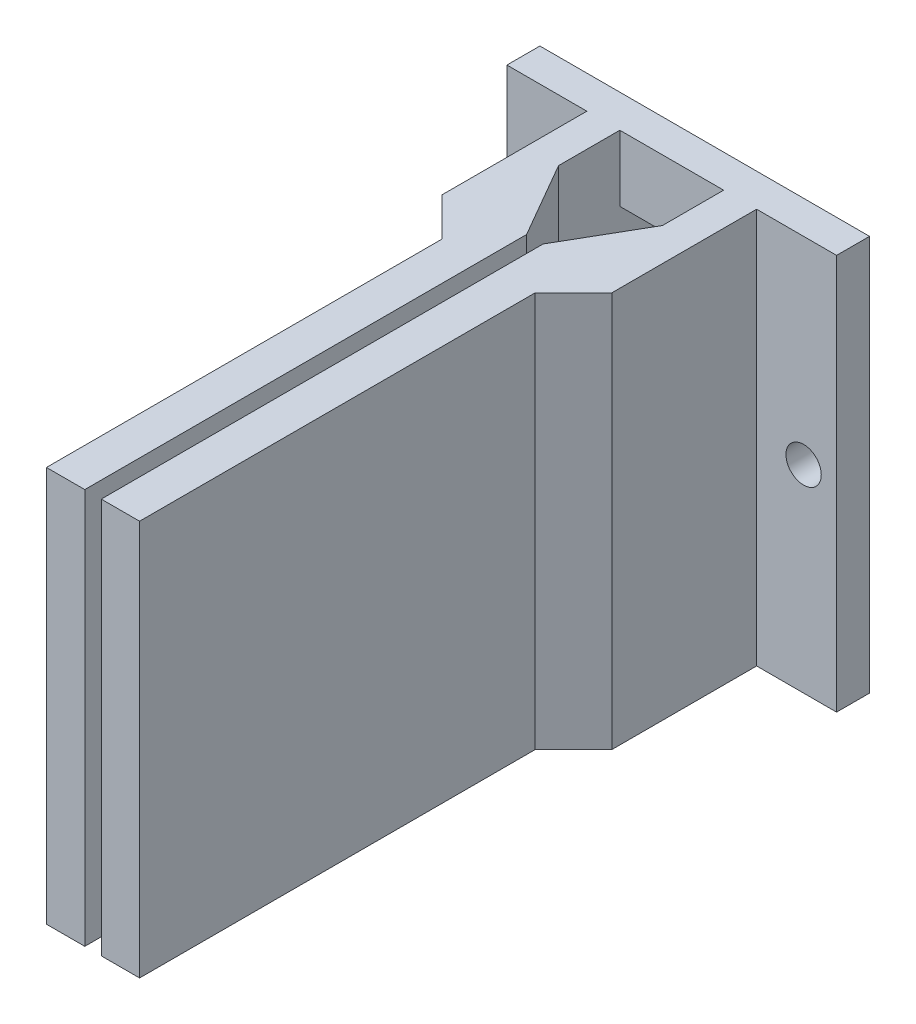
SolidWorks part; units mm, degrees
ref_plane "Front Plane" through (0, 0, 0) normal (0, 0, 1) x (1, 0, 0)
ref_plane "Top Plane" through (0, 0, 0) normal (0, 1, 0) x (1, 0, 0)
ref_plane "Right Plane" through (0, 0, 0) normal (1, 0, 0) x (0, 0, -1)
sketch "Sketch1" plane through (0, 0, 0) normal (0, 0, 1) x (1, 0, 0)
  line L1 (-5, -82.275) -> (5, -82.275)
  line L2 (-5, -82.275) -> (-5, 82.275)
  line L3 (-5, 82.275) -> (5, 82.275)
  line L4 (5, -82.275) -> (5, 82.275)
  line L5 (-5, -82.275) -> (5, 82.275) construction
  line L6 (-5, 82.275) -> (5, -82.275) construction
  line L7 (-5, 82.275) -> (5, 82.275)
  line L8 (-5, 82.275) -> (-5, 88.275)
  line L9 (-5, 88.275) -> (5, 88.275)
  line L10 (5, 82.275) -> (5, 88.275)
  circle A0 centre (0, 82.275) radius 2.5
  point P0 (0, 0)
  dimension "D3" = 5
  dimension "D1" = 164.55
  dimension "D2" = 10
  dimension "D4" = 6
extrude "Boss-Extrude1" add sketch "Sketch1" along normal blind 2 contours A0 L3 L2 L1 L4 | A0 L3 L10 L9 L8 region at (0, -0.4875, 0) region at (0, 85.6543, 0)
sketch "Sketch2" plane through (0, 0, 0) normal (0, 0, -1) x (-1, 0, 0)
  line L4 (5, 88.275) -> (-5, 88.275)
  line L5 (-5, 88.275) -> (-5, -82.275)
  line L6 (-5, -82.275) -> (5, -82.275)
  line L7 (5, -82.275) -> (5, 88.275)
  line L8 (5, 88.275) -> (-5, 88.275)
  line L9 (-5, 88.275) -> (-5, -82.275)
  line L10 (-5, -82.275) -> (5, -82.275)
  line L11 (5, -82.275) -> (5, 88.275)
  circle A0 centre (0, 82.275) radius 2.95
  dimension "D2" = 5.9
  dimension "D1" = 0
extrude "Boss-Extrude2" add sketch "Sketch2" along normal blind 1
sketch "Sketch3" plane through (0, -82.275, 0) normal (0, -1, 0) x (1, 0, 0)
  line L0 (5, -1) -> (-5, -1) construction
  line L1 (34.925, 9.16) -> (-34.925, 9.16)
  line L2 (34.925, 9.16) -> (34.925, -1)
  line L3 (34.925, -1) -> (-34.925, -1)
  line L4 (-34.925, 9.16) -> (-34.925, -1)
  circle A0 centre (28.575, 4.08) radius 1.8605
  circle A1 centre (-28.575, 4.08) radius 1.8605
  point P4 (0, -1)
  point P7 (0, -1)
  dimension "D3" = 3.7211
  dimension "D1" = 69.85
  dimension "D2" = 57.15
  dimension "D4" = 28.575
  dimension "D5" = 5.08
  dimension "D6" = 5.08
extrude "Boss-Extrude3" add sketch "Sketch3" against normal blind 2.5
fillet "Fillet1" radius 12.7 3 edges at (-5, -79.775, 0.5) (5, -79.775, 0.5) (0, -79.775, 2)
sketch "Sketch4" plane through (0, 0, -1) normal (0, 0, -1) x (-1, 0, 0)
  line L0 (5, -67.075) -> (5, 88.275) construction
  line L1 (8.175, 101.325) -> (5, 101.325)
  line L2 (8.175, 101.325) -> (8.175, 63.225)
  line L3 (8.175, 63.225) -> (5, 63.225)
  line L4 (5, 101.325) -> (5, 63.225)
  line L5 (-5, 101.325) -> (-8.175, 101.325)
  line L6 (-5, 101.325) -> (-5, 63.225)
  line L7 (-5, 63.225) -> (-8.175, 63.225)
  line L8 (-8.175, 101.325) -> (-8.175, 63.225)
  line L9 (-5, -67.075) -> (-5, 88.275) construction
  line L11 (5, 101.325) -> (-5, 101.325)
  line L12 (5, 101.325) -> (5, 88.275)
  line L13 (5, 88.275) -> (-5, 88.275)
  line L14 (-5, 101.325) -> (-5, 88.275)
  circle A0 centre (0, 82.275) radius 2.5 construction
  circle A1 centre (0, 82.275) radius 2.5 construction
  point P15 (8.175, 82.275)
  line M10 (-5, 88.275) -> (-5, -67.075)
  line M14 (5, -67.075) -> (5, 88.275)
  line M15 (5, 88.275) -> (-5, 88.275)
  dimension "D1" = 3.175
  dimension "D2" = 38.1
extrude "Boss-Extrude4" add sketch "Sketch4" against normal up to surface (3 mm away) contours L1 L4 L3 L2 M14 | L4 L11 L6 M15 | L5 L8 L7 L6 M10 region at (-6.5875, 82.275, -1) region at (0, 94.8, -1) region at (6.5875, 82.275, -1) up to face at (0, -15.7159, 2)
extrude "Boss-Extrude5" add sketch "Sketch4<3>" against normal blind 11.1125 contours L1 L2 L3 L4 | L6 L7 L8 L5
sketch "Sketch4<3>" plane through (0, 0, -1) normal (0, 0, -1) x (-1, 0, 0) same geometry as "Sketch4"
sketch "Sketch5" plane through (0, 0, 10.1125) normal (0, 0, 1) x (1, 0, 0)
  line L0 (5, 63.225) -> (8.175, 63.225) construction
  line L1 (-8.175, 101.325) -> (-0.7937, 101.325)
  line L2 (-8.175, 101.325) -> (-8.175, 63.225)
  line L3 (-8.175, 63.225) -> (-0.7937, 63.225)
  line L4 (-0.7937, 101.325) -> (-0.7937, 63.225)
  line L5 (8.175, 101.325) -> (0.7938, 101.325)
  line L6 (8.175, 101.325) -> (8.175, 63.225)
  line L7 (8.175, 63.225) -> (0.7938, 63.225)
  line L8 (0.7938, 101.325) -> (0.7938, 63.225)
  dimension "D1" = 1.5875
extrude "Boss-Extrude6" add sketch "Sketch5" along normal blind 50.8
sketch "Sketch6" plane through (0, 0, 60.9125) normal (0, 0, 1) x (1, 0, 0)
  line L0 (-8.175, 63.225) -> (-0.7937, 63.225) construction
  line L1 (-8.175, 101.325) -> (-4.4844, 101.325)
  line L2 (-8.175, 101.325) -> (-8.175, 63.225)
  line L3 (-8.175, 63.225) -> (-4.4844, 63.225)
  line L4 (-4.4844, 101.325) -> (-4.4844, 63.225)
  line L5 (0.7938, 63.225) -> (8.175, 63.225) construction
  line L6 (8.175, 101.325) -> (4.4844, 101.325)
  line L7 (8.175, 101.325) -> (8.175, 63.225)
  line L8 (8.175, 63.225) -> (4.4844, 63.225)
  line L9 (4.4844, 101.325) -> (4.4844, 63.225)
extrude "Cut-Extrude1" cut sketch "Sketch6" against normal blind 44.45
chamfer "Chamfer1" distance 4.7625 angle 60 2 edges at (-0.7937, 82.275, 10.1125) (0.7938, 82.275, 10.1125) first distance on face at (-2.8969, 82.275, 10.1125) first distance on face at (2.8969, 82.275, 10.1125)
sketch "Sketch7" plane through (0, -82.275, 0) normal (0, -1, 0) x (1, 0, 0)
  line L4 (-34.925, 9.16) -> (-34.925, -1)
  line L5 (-34.925, -1) -> (34.925, -1)
  line L6 (34.925, -1) -> (34.925, 9.16)
  line L7 (34.925, 9.16) -> (-34.925, 9.16)
  line L8 (-34.925, 9.16) -> (-34.925, -1)
  line L9 (-34.925, -1) -> (34.925, -1)
  line L10 (34.925, -1) -> (34.925, 9.16)
  line L11 (34.925, 9.16) -> (-34.925, 9.16)
  dimension "D1" = 0
extrude "Cut-Extrude2" cut sketch "Sketch7" against normal up to surface (145.5 mm away) up to face at (4.6563, 63.225, 20.4653)
sketch "Sketch8" plane through (0, 0, 2) normal (0, 0, -1) x (-1, 0, 0)
  line L0 (8.175, 101.325) -> (-8.175, 101.325) construction
  line L1 (-15.875, 63.225) -> (15.875, 63.225)
  line L2 (-15.875, 63.225) -> (-15.875, 101.325)
  line L3 (-15.875, 101.325) -> (15.875, 101.325)
  line L4 (15.875, 63.225) -> (15.875, 101.325)
  line L5 (-15.875, 63.225) -> (15.875, 101.325) construction
  line L6 (-15.875, 101.325) -> (15.875, 63.225) construction
  line L7 (-12.7, 82.275) -> (12.7, 82.275) construction
  point P0 (0, 82.275)
  point P10 (0, 82.275)
  dimension "D1" = 25.4
  dimension "D2" = 31.75
extrude "Boss-Extrude7" add sketch "Sketch8" against normal blind 3.175
sketch "Sketch9" plane through (0, 101.325, 0) normal (0, 1, 0) x (1, 0, 0)
  line L0 (-5, -11.076) -> (-5, -5.175) construction
  line L1 (8.175, 1) -> (-8.175, 1)
  line L2 (8.175, 1) -> (8.175, -2)
  line L3 (8.175, -2) -> (-8.175, -2)
  line L4 (-8.175, 1) -> (-8.175, -2)
  line L5 (5, -5.175) -> (-5, -5.175)
  line L6 (5, -5.175) -> (5, -2)
  line L7 (5, -2) -> (-5, -2)
  line L8 (-5, -5.175) -> (-5, -2)
  line M6 (8.175, -2) -> (8.175, 1)
  line M7 (8.175, 1) -> (-8.175, 1)
  line M8 (-8.175, 1) -> (-8.175, -2)
  line M19 (-5, -5.175) -> (5, -5.175)
extrude "Cut-Extrude3" cut sketch "Sketch9" against normal through all contours L8 L6 L3 M19 | L3 M6 M7 M8 region at (0, 101.325, 0.5) region at (0, 101.325, 3.5875)
chamfer "Chamfer2" distance 6.35 angle 45 1 edges at (4.4844, 82.275, 16.4625)
chamfer "Chamfer3" distance 6.35 angle 45 1 edges at (-4.4844, 82.275, 16.4625)
hole_wizard "M3 Clearance Hole1" positions "Sketch10" profile "Sketch11" hole size "M3" standard "ANSI Metric" end condition through all
sketch "Sketch10" plane through (0, 0, 2) normal (0, 0, -1) x (-1, 0, 0)
  point P0 (12.7, 82.275)
  point P3 (-12.7, 82.275)
sketch "Sketch11" plane through (-12.7, 82.275, 2) normal (1, 0, 0) x (0, 1, 0)
  line L0 (0, 0) -> (0, 58.9125)
  line L1 (0, 58.9125) -> (1.7, 58.9125)
  line L2 (1.7, 58.9125) -> (1.7, 0)
  line L5 (1.7, 0) -> (0, 0)
  line L11 (0, -6.35) -> (0, 107.95) construction
  dimension "Thru Hole Dia." = 3.4
  dimension "Thru Hole Depth" = 58.9125
sketch "Sketch13" plane through (0, 0, 2) normal (0, 0, -1) x (-1, 0, 0)
  line L0 (5, 63.225) -> (5, 101.325) construction
  line L1 (-5, 101.325) -> (5, 101.325)
  line L2 (-5, 101.325) -> (-5, 94.975)
  line L3 (-5, 94.975) -> (5, 94.975)
  line L4 (5, 101.325) -> (5, 94.975)
  line L5 (-5, 63.225) -> (-5, 101.325) construction
  line L6 (5, 63.225) -> (-5, 63.225)
  line L7 (5, 63.225) -> (5, 69.575)
  line L8 (5, 69.575) -> (-5, 69.575)
  line L9 (-5, 63.225) -> (-5, 69.575)
  dimension "D1" = 6.35
extrude "Boss-Extrude8" add sketch "Sketch13" against normal blind 3.175
